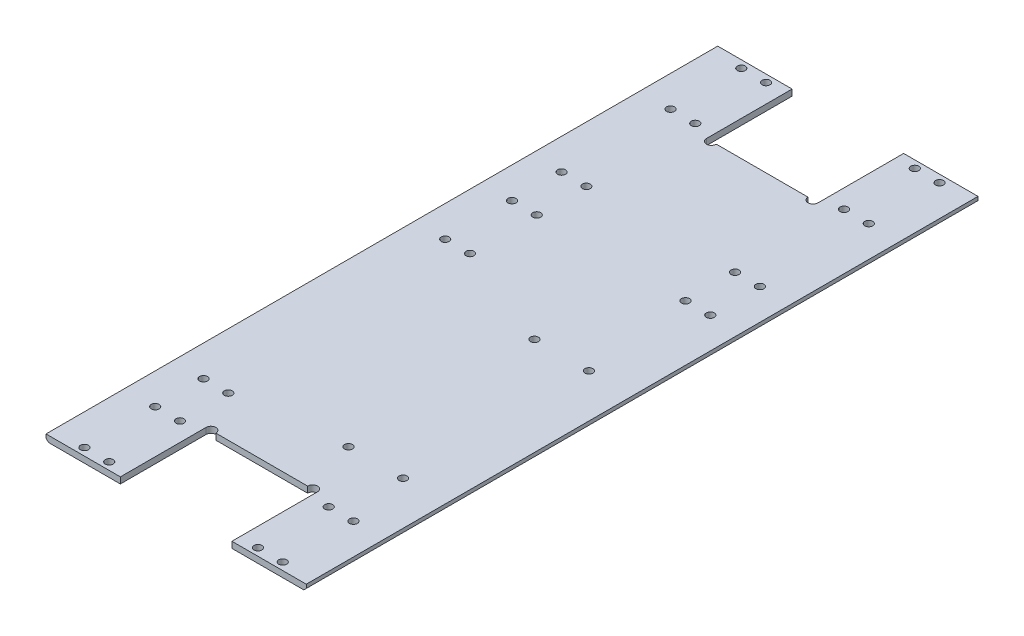
SolidWorks part; units mm, degrees
ref_plane "前视基准面" through (0, 0, 0) normal (0, 0, 1) x (1, 0, 0)
ref_plane "上视基准面" through (0, 0, 0) normal (0, 1, 0) x (1, 0, 0)
ref_plane "右视基准面" through (0, 0, 0) normal (1, 0, 0) x (0, 0, -1)
sketch "草图1" plane through (0, 0, 0) normal (0, 1, 0) x (1, 0, 0)
  line L6 (-52.5, -135.5) -> (52.5, -135.5)
  line L7 (52.5, -135.5) -> (52.5, 135.5)
  line L8 (-52.5, 135.5) -> (52.5, 135.5)
  line L9 (-52.5, -135.5) -> (-52.5, 135.5)
  point P8 (-50, 0)
extrude "凸台-拉伸1" add sketch "草图1" along normal blind 2.5
sketch "草图2" plane through (0, 2.5, 0) normal (0, 1, 0) x (1, 0, 0)
  circle A20 centre (13, -3.95) radius 1.6
  circle A21 centre (35, -3.95) radius 1.6
  circle A24 centre (35, -78.95) radius 1.6
  circle A25 centre (13, -78.95) radius 1.6
extrude "切除-拉伸1" cut sketch "草图2" against normal blind 10
chamfer "倒角4" distance 1 angle 45 2 edges at (52.5, 0, 0) (-52.5, 0, 0)
sketch "草图3" plane through (0, 0, 0) normal (0, -1, 0) x (1, 0, 0)
  line L0 (-22.5, 100.95) -> (22.5, 100.95)
  line L2 (-51.5, 135.5) -> (51.5, 135.5) construction
  line L3 (1.375, 0) -> (-1.375, 0) construction
  line L4 (22.5, 100.95) -> (22.5, 135.5)
  line L5 (22.5, 135.5) -> (-22.5, 135.5)
  line L6 (-22.5, 135.5) -> (-22.5, 100.95)
  line L7 (-22.5, -135.5) -> (-22.5, -100.95)
  line L8 (22.5, -135.5) -> (-22.5, -135.5)
  line L9 (22.5, -100.95) -> (22.5, -135.5)
  line L10 (-22.5, -100.95) -> (22.5, -100.95)
extrude "切除-拉伸2" cut sketch "草图3" against normal blind 10
sketch "草图4" plane through (0, 0, 0) normal (0, -1, 0) x (1, 0, 0)
  line L0 (0, -1.375) -> (0, 1.375) construction
  line L1 (22.5, -100.95) -> (-22.5, -100.95) construction
  line L2 (1.375, 0) -> (-1.375, 0) construction
  circle A0 centre (20.5, -100.95) radius 2
  circle A1 centre (-20.5, -100.95) radius 2
  circle A2 centre (-20.5, 100.95) radius 2
  circle A3 centre (20.5, 100.95) radius 2
extrude "切除-拉伸3" cut sketch "草图4" against normal blind 10
sketch "草图5" plane through (0, 2.5, 0) normal (0, 1, 0) x (1, 0, 0)
  line L0 (0, -1.375) -> (0, 1.375) construction
  line L3 (-1.375, 0) -> (1.375, 0) construction
  circle A0 centre (-40, 103.95) radius 1.6
  circle A1 centre (-30, 103.95) radius 1.6
  circle A4 centre (-40, 132.5) radius 1.6
  circle A5 centre (-30, 132.5) radius 1.6
  circle A6 centre (30, 132.5) radius 1.6
  circle A7 centre (40, 132.5) radius 1.6
  circle A8 centre (30, 103.95) radius 1.6
  circle A9 centre (40, 103.95) radius 1.6
  circle A10 centre (40, -103.95) radius 1.6
  circle A11 centre (30, -103.95) radius 1.6
  circle A12 centre (40, -132.5) radius 1.6
  circle A13 centre (30, -132.5) radius 1.6
  circle A14 centre (-30, -132.5) radius 1.6
  circle A15 centre (-40, -132.5) radius 1.6
  circle A16 centre (-30, -103.95) radius 1.6
  circle A17 centre (-40, -103.95) radius 1.6
extrude "切除-拉伸4" cut sketch "草图5" against normal blind 10
sketch "草图6" plane through (0, 2.5, 0) normal (0, 1, 0) x (1, 0, 0)
  line L0 (0, -1.375) -> (0, 1.375) construction
  circle A0 centre (40, 60) radius 1.6
  circle A1 centre (30, 60) radius 1.6
  circle A2 centre (40, 40) radius 1.6
  circle A3 centre (30, 40) radius 1.6
  circle A4 centre (-30, 40) radius 1.6
  circle A5 centre (-40, 40) radius 1.6
  circle A6 centre (-30, 60) radius 1.6
  circle A7 centre (-40, 60) radius 1.6
  circle A8 centre (-30, -84.45) radius 1.6
  circle A9 centre (-40, -84.45) radius 1.6
  circle A10 centre (-30, 13.05) radius 1.6
  circle A11 centre (-40, 13.05) radius 1.6
  point P34 (-40, 13.05)
  point P35 (-30, 13.05)
  dimension "D1" = 2
extrude "切除-拉伸5" cut sketch "草图6" against normal blind 10
